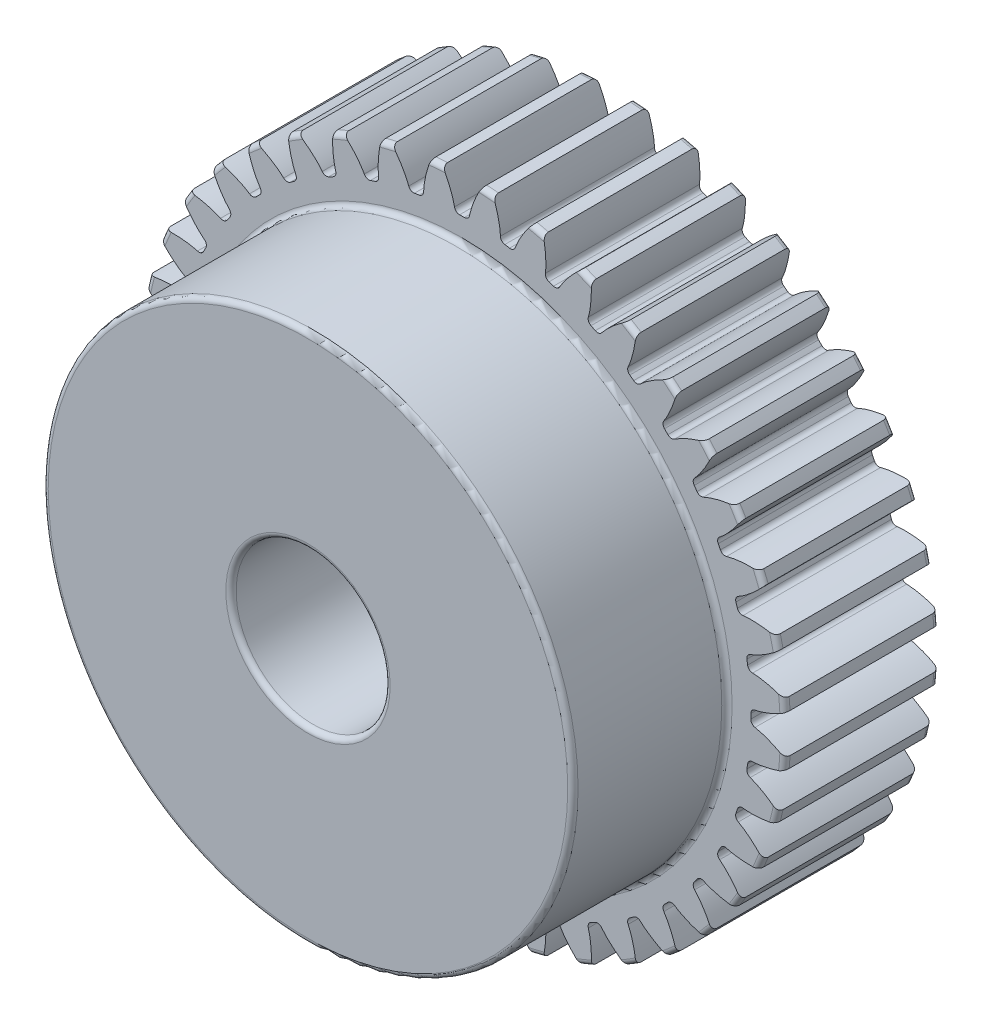
SolidWorks part; units mm, degrees
ref_plane "Front Plane" through (0, 0, 0) normal (0, 0, 1) x (1, 0, 0)
ref_plane "Top Plane" through (0, 0, 0) normal (0, 1, 0) x (1, 0, 0)
ref_plane "Right Plane" through (0, 0, 0) normal (1, 0, 0) x (0, 0, -1)
sketch "Sketch1" plane through (0, 0, 0) normal (0, 0, 1) x (1, 0, 0)
  line L0 (0, 0) -> (0, 25.4) construction
  line L1 (-8.1634, 28.3712) -> (8.1634, 22.4288) construction
  circle A0 centre (0, 0) radius 23.8125 construction
  circle A1 centre (0, 0) radius 26.67 construction
  circle A2 centre (0, 0) radius 25.4 construction
  circle A3 centre (0, 0) radius 23.8682 construction
  circle A4 centre (0, 0) radius 6.35 construction
  circle A5 centre (0, 0) radius 21.844 construction
  point P8 (254, 0)
  point P13 (508, 0)
  dimension "OD | Outside Diameter" = 53.34
  dimension "Root Diameter" = 47.625
  dimension "Gear Pitch Diameter" = 50.8
  dimension "Base Diameter" = 47.7364
  dimension "For Shaft Diameter" = 12.7
  dimension "Hub Diameter" = 43.688
  dimension "Pressure Angle" = 20
  dimension "Number of Teeth" = 1016
  dimension "Gear Pitch | Diametral Pitch" = 508
sketch "Sketch2" plane through (0, 0, 0) normal (1, 0, 0) x (0, 0, -1)
  line L0 (-12.7, 0) -> (12.7, 0) construction
  line L1 (-12.7, 26.67) -> (12.7, 26.67) construction
  point P2 (0, 26.67)
  point P4 (0, 0)
  point P6 (0, 26.67)
  dimension "Overall Width" = 25.4
  dimension "Hub Width" = 12.7
  dimension "Face Width" = 12.7
sketch "Sketch3" plane through (0, 0, 0) normal (0, 0, 1) x (1, 0, 0)
  circle A0 centre (0, 0) radius 26.67
  circle A1 centre (0, 0) radius 26.67 construction
extrude "Boss-Extrude1" add sketch "Sketch3" against normal up to vertex (12.7 mm away) and the other way up to vertex (12.7 mm away) up to point (0, 0, -12.7) other way up to point (0, 0, 12.7)
sketch "Sketch5" plane through (0, 0, 0) normal (1, 0, 0) x (0, 0, -1)
  line L1 (-12.7, 26.67) -> (0, 26.67)
  line L2 (-12.7, 26.67) -> (-12.7, 21.844)
  line L3 (-12.7, 21.844) -> (0, 21.844)
  line L4 (0, 26.67) -> (0, 21.844)
  line L11 (12.7, 6.35) -> (-12.7, 6.35)
  line L12 (12.7, 6.35) -> (12.7, 0)
  line L13 (12.7, 0) -> (-12.7, 0)
  line L14 (-12.7, 6.35) -> (-12.7, 0)
  point P5 (0, 6.35)
  point P12 (0, 21.844)
revolve "Cut-Revolve1" cut sketch "Sketch5" angle 360 about L0
fillet "Fillet2" radius 0.4261 6 edges at (26.67, 0, -12.7) (6.35, 0, -12.7) (6.35, 0, 12.7) (21.844, 0, 0) (26.67, 0, 0) (21.844, 0, 12.7)
sketch "Sketch4" plane through (0, 0, 0) normal (0, 0, 1) x (1, 0, 0)
  line L0 (0, 0) -> (23.8054, 0.5801) construction
  line L2 (0, 0) -> (23.8054, -0.5801) construction
  line L4 (23.8054, 0.5801) -> (23.8611, 0.5815)
  line L5 (23.8611, -0.5815) -> (23.8054, -0.5801)
  arc A0 (23.8054, 0.5801) -> (23.8054, -0.5801) centre (0, 0) cw
  arc A3 (26.6213, 1.6107) -> (26.6213, -1.6107) centre (0, 0) cw
  circle A4 centre (0, 0) radius 26.67 construction
  spline S0 degree 4 poles (23.8611, 0.5815) (23.8655, 0.5817) (23.8778, 0.5822) (23.901, 0.5839) (23.9389, 0.5874) (23.9871, 0.593) (24.0493, 0.6016) (24.1225, 0.6136) (24.2029, 0.6285) (24.2903, 0.6467) (24.3773, 0.6666) (24.464, 0.6881) (24.5503, 0.711) (24.6546, 0.7404) (24.7796, 0.7781) (24.9253, 0.8257) (25.0903, 0.8838) (25.2579, 0.9474) (25.4225, 1.0136) (25.5884, 1.0847) (25.7486, 1.1565) (25.9145, 1.2353) (26.0673, 1.3103) (26.238, 1.3989) (26.3756, 1.4719) (26.5565, 1.5732) (26.6631, 1.6345) (26.7877, 1.708) (26.8429, 1.7415) (26.8769, 1.7622) knots 0 0 0 0 0 0.005377 0.015084 0.028532 0.04661 0.064855 0.092111 0.119476 0.146842 0.174209 0.201575 0.228941 0.256307 0.307035 0.361767 0.4165 0.471232 0.525964 0.580697 0.635429 0.690161 0.744894 0.799626 0.854358 0.909091 0.954545 1 1 1 1 1 construction
  spline S1 degree 4 poles (23.8611, 0.5815) (23.8655, 0.5817) (23.8778, 0.5822) (23.901, 0.5839) (23.9389, 0.5874) (23.9871, 0.593) (24.0493, 0.6016) (24.1225, 0.6136) (24.2029, 0.6285) (24.2903, 0.6467) (24.3773, 0.6666) (24.464, 0.6881) (24.5503, 0.711) (24.6546, 0.7404) (24.7796, 0.7781) (24.9253, 0.8257) (25.0903, 0.8838) (25.2579, 0.9474) (25.4225, 1.0136) (25.5884, 1.0847) (25.7486, 1.1565) (25.9145, 1.2353) (26.0673, 1.3103) (26.238, 1.3989) (26.3756, 1.4719) (26.5173, 1.5512) (26.5862, 1.5904) (26.6213, 1.6107) knots 0 0 0 0 0 0.005377 0.015084 0.028532 0.04661 0.064855 0.092111 0.119476 0.146842 0.174209 0.201575 0.228941 0.256307 0.307035 0.361767 0.4165 0.471232 0.525964 0.580697 0.635429 0.690161 0.744894 0.799626 0.854358 0.909091 0.909091 0.909091 0.909091 0.909091
  spline S2 degree 4 poles (23.8611, -0.5815) (23.8655, -0.5817) (23.8778, -0.5822) (23.901, -0.5839) (23.9389, -0.5874) (23.9871, -0.593) (24.0493, -0.6016) (24.1225, -0.6136) (24.2029, -0.6285) (24.2903, -0.6467) (24.3773, -0.6666) (24.464, -0.6881) (24.5503, -0.711) (24.6546, -0.7404) (24.7796, -0.7781) (24.9253, -0.8257) (25.0903, -0.8838) (25.2579, -0.9474) (25.4225, -1.0136) (25.5884, -1.0847) (25.7486, -1.1565) (25.9145, -1.2353) (26.0673, -1.3103) (26.238, -1.3989) (26.3756, -1.4719) (26.5565, -1.5732) (26.6631, -1.6345) (26.7877, -1.708) (26.8429, -1.7415) (26.8769, -1.7622) knots 0 0 0 0 0 0.005377 0.015084 0.028532 0.04661 0.064855 0.092111 0.119476 0.146842 0.174209 0.201575 0.228941 0.256307 0.307035 0.361767 0.4165 0.471232 0.525964 0.580697 0.635429 0.690161 0.744894 0.799626 0.854358 0.909091 0.954545 1 1 1 1 1 construction
  spline S3 degree 4 poles (23.8611, -0.5815) (23.8655, -0.5817) (23.8778, -0.5822) (23.901, -0.5839) (23.9389, -0.5874) (23.9871, -0.593) (24.0493, -0.6016) (24.1225, -0.6136) (24.2029, -0.6285) (24.2903, -0.6467) (24.3773, -0.6666) (24.464, -0.6881) (24.5503, -0.711) (24.6546, -0.7404) (24.7796, -0.7781) (24.9253, -0.8257) (25.0903, -0.8838) (25.2579, -0.9474) (25.4225, -1.0136) (25.5884, -1.0847) (25.7486, -1.1565) (25.9145, -1.2353) (26.0673, -1.3103) (26.238, -1.3989) (26.3756, -1.4719) (26.5173, -1.5512) (26.5862, -1.5904) (26.6213, -1.6107) knots 0 0 0 0 0 0.005377 0.015084 0.028532 0.04661 0.064855 0.092111 0.119476 0.146842 0.174209 0.201575 0.228941 0.256307 0.307035 0.361767 0.4165 0.471232 0.525964 0.580697 0.635429 0.690161 0.744894 0.799626 0.854358 0.909091 0.909091 0.909091 0.909091 0.909091
  dimension "D1" = 47.625
extrude "Cut-Extrude1" cut sketch "Sketch4" against normal through all both and the other way through all
fillet "Fillet1" radius 0.4261 2 edges at (23.8054, -0.5801, -6.35) (23.8054, 0.5801, -6.35)
pattern_circular "CirPattern1" count 40 over 360 about axis through (0, 0, 12.7) along (0, 0, -1) of "Cut-Extrude1", "Fillet1"
equation "\"Root Diameter@Sketch1\"=\"Root Diameter\""
equation "\"OD | Outside Diameter@Sketch1\"=\"Outside Diameter\""
equation "\"D1@CirPattern1\"=\"Number of Teeth\""
equation "\"Diametral Pitch\"=20"
equation "\"Number of Teeth\"= 40"
equation "\"Pressure Angle\"=20"
equation "\"Pitch Diameter\"= \"Number of Teeth\" / \"Diametral Pitch\""
equation "\"Base Diameter\"= \"Pitch Diameter\" * cos ( \"Pressure Angle\" )"
equation "\"Outside Diameter\"= ( \"Number of Teeth\" + 2 ) / \"Diametral Pitch\""
equation "\"Dedendum\"= 1.25 / \"Diametral Pitch\""
equation "\"Root Diameter\"= \"Pitch Diameter\" - ( 2 * \"Dedendum\" )"
equation "\"Pitch Angle\"= 360deg / \"Number of Teeth\""
equation "\"Alpha\"= sqr ( \"Pitch Diameter\" ^ 2 - \"Base Diameter\" ^ 2 ) / \"Base Diameter\" * 180 / PI - \"Pressure Angle\""
equation "\"Beta\"= ( \"Pitch Angle\" / 4 - \"Alpha\" )"
equation "\"Phi\"= sqr ( ( \"Outside Diameter\" / 2 ) ^ 2 - ( \"Base Diameter\" / 2 ) ^ 2 ) / ( \"Base Diameter\" / 2 )"
equation "\"Addendum\"= 1 / \"Diametral Pitch\""
equation "\"WorkingDepth\"= 2 / \"Diametral Pitch\""
equation "\"WholeDepth\"= 2.25 / \"Diametral Pitch\""
equation "\"Clearance\"= 0.25 / \"Diametral Pitch\""
equation "\"ToothThickness\"= ( pi * 2 ) / \"Diametral Pitch\""
equation "\"CircularPitch\"= pi / \"Diametral Pitch\""
equation "\"Number of Teeth@Sketch1\"=\"Number of Teeth\""
equation "\"Gear Pitch | Diametral Pitch@Sketch1\"=\"Diametral Pitch\""
equation "\"Pressure Angle@Sketch1\"=\"Pressure Angle\""
equation "\"Gear Pitch Diameter@Sketch1\"=\"Pitch Diameter\""
equation "\"Base Diameter@Sketch1\"=\"Base Diameter\""
equation "\"Fillet\"= \"Clearance\" * cos ( \"Pressure Angle\" ) * tan ( ( 90 + \"Pressure Angle\" ) / 2 )"
equation "\"D1@Fillet1\"=\"Fillet\""
equation "\"D1@Sketch4\"=if( \"Base Diameter\">\"Root Diameter\",\"Root Diameter\",\"Base Diameter\"-.00001)"
equation "\"D1@Fillet2\"=\"Fillet\""
